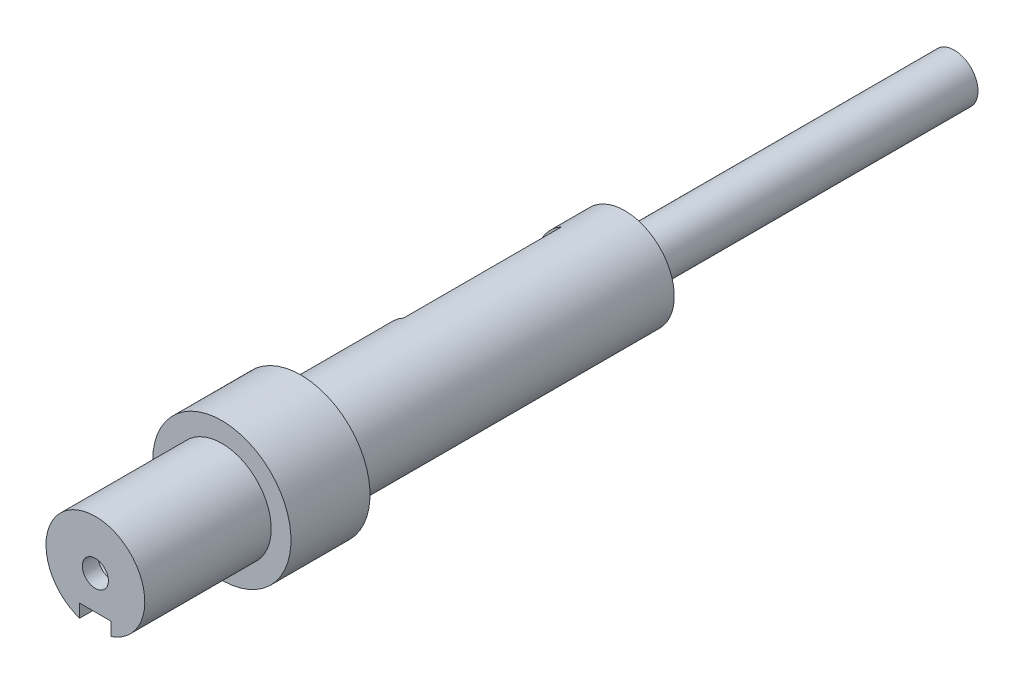
SolidWorks part; units mm, degrees
ref_plane "Plan de face" through (0, 0, 0) normal (0, 0, 1) x (1, 0, 0)
ref_plane "Plan de dessus" through (0, 0, 0) normal (0, 1, 0) x (1, 0, 0)
ref_plane "Plan de droite" through (0, 0, 0) normal (1, 0, 0) x (0, 0, -1)
sketch "Esquisse1" plane through (0, 0, 0) normal (0, 0, 1) x (1, 0, 0)
  circle A0 centre (0, 0) radius 30
  dimension "D1" = 60
extrude "Boss.-Extru.1" add sketch "Esquisse1" along normal blind 15
sketch "Esquisse2" plane through (0, 0, 0) normal (0, 0, -1) x (-1, 0, 0)
  circle A0 centre (0, 0) radius 12.5
  dimension "D1" = 25
extrude "Boss.-Extru.2" add sketch "Esquisse2" along normal blind 124
sketch "Esquisse4" plane through (0, 0, 15) normal (0, 0, 1) x (1, 0, 0)
  line L1 (115, 20) -> (-115, 20)
  line L2 (115, 20) -> (115, -20)
  line L3 (115, -20) -> (-115, -20)
  line L4 (-115, 20) -> (-115, -20)
  line L5 (115, 20) -> (-115, -20) construction
  line L6 (115, -20) -> (-115, 20) construction
  point P0 (0, 0)
  dimension "D1" = 40
  dimension "D2" = 230
extrude "Boss.-Extru.3" [suppressed] add sketch "Esquisse4" along normal blind 5
extrude "Enlèv. mat.-Extru.1" cut sketch "Esquisse4<2>" against normal blind 5
sketch "Esquisse4<2>" plane through (0, 0, 15) normal (0, 0, 1) x (1, 0, 0) same geometry as "Esquisse4"
sketch "Esquisse6" plane through (0, 0, 0) normal (0, 0, -1) x (-1, 0, 0)
  circle A2 centre (0, 0) radius 20.5
  circle A3 centre (0, 0) radius 20.5 construction
  dimension "D1" = 8
hole_wizard "Chambrage pour vis à tête hexagonale M51" positions "Esquisse15" profile "Esquisse14" counterbore size "M5" standard "Ansi Metric" end condition through all
sketch "Esquisse15" plane through (0, 0, 0) normal (0, 0, -1) x (-1, 0, 0)
  circle A0 centre (0, 0) radius 20.5 construction
  point P0 (20.5, 0)
  point P4 (-20.5, 0)
sketch "Esquisse14" plane through (-20.5, 0, 0) normal (1, 0, 0) x (0, 1, 0)
  line L0 (0, 0) -> (0, 15)
  line L1 (0, 15) -> (2.75, 15)
  line L2 (2.75, 3.605) -> (2.75, 15)
  line L3 (2.75, 3.605) -> (2.775, 3.58)
  line L4 (2.775, 3.58) -> (6.12, 3.58)
  line L5 (6.12, 3.58) -> (6.12, 0)
  line L7 (0, 0) -> (6.12, 0)
  line L9 (-2.75, 3.605) -> (-2.775, 3.58) construction
  line L11 (0, -6.35) -> (0, 107.95) construction
  dimension "Diamètre du perçage jusqu'au prochain" = 5.5
  dimension "Profondeur du perçage jusqu'au prochain" = 15
  dimension "Diamètre du chambrage" = 12.24
  dimension "Profondeur du chambrage" = 3.58
  dimension "Diamètre du fraisage milieu" = 5.55
  dimension "Angle du fraisage milieu" = 90
sketch "Esquisse17" plane through (0, 0, -124) normal (0, 0, -1) x (-1, 0, 0)
  circle A0 centre (0, 0) radius 6
  dimension "D1" = 12
extrude "Boss.-Extru.4" add sketch "Esquisse17" along normal blind 83.38
sketch "Esquisse18" plane through (0, 0, -207.38) normal (0, 0, -1) x (-1, 0, 0)
  line L0 (6.9654, 0) -> (-3.391, 0) construction
  line L1 (-3.391, 1.5) -> (6.9654, 1.5)
  line L2 (-3.391, 1.5) -> (-3.391, -1.5)
  line L3 (-3.391, -1.5) -> (6.9654, -1.5)
  line L4 (6.9654, 1.5) -> (6.9654, -1.5)
  line L5 (-3.391, 1.5) -> (6.9654, -1.5) construction
  line L6 (-3.391, -1.5) -> (6.9654, 1.5) construction
  point P0 (-0.771, 0)
  dimension "D1" = 3
  dimension "D2" = 2.62
extrude "Enlèv. mat.-Extru.2" cut sketch "Esquisse18" against normal blind 3
sketch "Esquisse19" plane through (0, 0, -124) normal (0, 0, -1) x (-1, 0, 0)
  line L0 (6, 10.9659) -> (6, -10.9659)
  line L1 (6, 10.9659) -> (13.9334, 10.9659)
  line L2 (6, -10.9659) -> (13.9334, -10.9659)
  line L3 (13.9334, 10.9659) -> (13.9334, -10.9659)
  circle A0 centre (0, 0) radius 12.5 construction
  circle A1 centre (0, 0) radius 12.5 construction
extrude "Enlèv. mat.-Extru.3" cut sketch "Esquisse19" against normal blind 50
sketch "Esquisse21" plane through (0, 0, -124) normal (0, 0, -1) x (-1, 0, 0)
  circle A0 centre (0, 0) radius 12.5
extrude "Boss.-Extru.6" add sketch "Esquisse21" against normal blind 10
hole_wizard "Dégagement M41" positions "Esquisse23" profile "Esquisse22" hole size "M4" standard "JIS"
sketch "Esquisse23" plane through (-6, 0, 0) normal (-1, 0, 0) x (0, 0, 1)
  point P0 (-82.1, 5.8507)
  point P2 (-93.1, -2.1493)
  point P4 (-93.1, 5.8507)
  point P6 (-104.1, 5.8507)
sketch "Esquisse22" plane through (-6, 5.8507, -82.1) normal (0, 1, 0) x (0, 0, 1)
  line L0 (0, 0) -> (0, 4.299)
  line L1 (0, 4.299) -> (2.25, 3)
  line L2 (2.25, 3) -> (2.25, 0)
  line L5 (2.25, 0) -> (0, 0)
  line L10 (0, 4.299) -> (-2.25, 3) construction
  line L11 (0, -6.35) -> (0, 107.95) construction
  dimension "Diamètre du perçage" = 4.5
  dimension "Profondeur du perçage" = 3
  dimension "Angle de pointe" = 120
sketch "Esquisse26" plane through (0, 0, -74) normal (0, 0, -1) x (-1, 0, 0)
  circle A0 centre (0, 0) radius 17.5
  dimension "D1" = 35
extrude "Boss.-Extru.8" add sketch "Esquisse26" against normal blind 52
sketch "Esquisse27" plane through (0, 0, -74) normal (0, 0, -1) x (-1, 0, 0)
  circle A0 centre (0, 0) radius 17.5
  circle A1 centre (0, 0) radius 12.5
  arc M2 (6, -10.9659) -> (6, 10.9659) centre (0, 0) cw
  circle M3 centre (0, 0) radius 17.5
  dimension "D1" = 25
extrude "Enlèv. mat.-Extru.5" cut sketch "Esquisse27" against normal blind 32 contours A1 M3 M2 region at (17.005, 0, -74)
sketch "Esquisse28" plane through (0, 0, 15) normal (0, 0, 1) x (1, 0, 0)
  circle A0 centre (0, 0) radius 30
  dimension "D1" = 60
extrude "Enlèv. mat.-Extru.6" cut sketch "Esquisse28" against normal blind 15
sketch "Esquisse29" plane through (0, 0, 0) normal (0, 0, 1) x (1, 0, 0)
  line L0 (0, 0) -> (0, -17.5) construction
  line L1 (-4, -8.5) -> (4, -8.5)
  line L2 (-4, -8.5) -> (-4, -15.8)
  line L3 (-4, -15.8) -> (4, -15.8)
  line L4 (4, -8.5) -> (4, -15.8)
  line L5 (-4, -8.5) -> (4, -15.8) construction
  line L6 (-4, -15.8) -> (4, -8.5) construction
  circle A0 centre (0, 0) radius 12.5
  circle A1 centre (0, 0) radius 17.5 construction
  circle M6 centre (0, 0) radius 12.5
  dimension "D1" = 25
  dimension "D2" = 15.8
  dimension "D3" = 8
  dimension "D4" = 4
  dimension "D5" = 8.5
extrude "Boss.-Extru.9" add sketch "Esquisse29" along normal blind 10 contours A0 L2 L1 L4 M6 region at (0, 0.6832, 0)
hole_wizard "Dégagement M61" positions "Esquisse31" profile "Esquisse30" hole size "M6" standard "JIS"
sketch "Esquisse31" plane through (0, 0, 10) normal (0, 0, 1) x (1, 0, 0)
  point P0 (0, 0)
sketch "Esquisse30" plane through (0, 0, 10) normal (1, 0, 0) x (0, -1, 0)
  line L0 (0, 0) -> (0, 5.9053)
  line L1 (0, 5.9053) -> (3.3, 4)
  line L2 (3.3, 4) -> (3.3, 0)
  line L5 (3.3, 0) -> (0, 0)
  line L10 (0, 5.9053) -> (-3.3, 4) construction
  line L11 (0, -6.35) -> (0, 107.95) construction
  dimension "Diamètre du perçage" = 6.6
  dimension "Profondeur du perçage" = 4
  dimension "Angle de pointe" = 120
